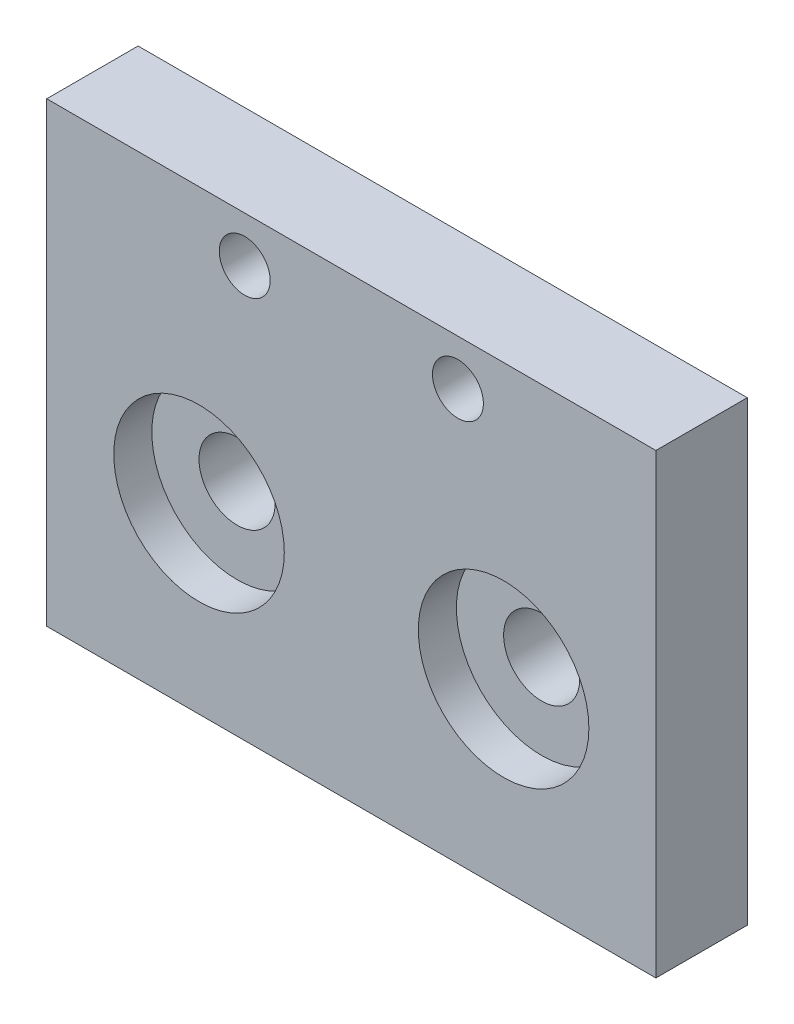
SolidWorks part; units mm, degrees
ref_plane "Front Plane" through (0, 0, 0) normal (0, 0, 1) x (1, 0, 0)
ref_plane "Top Plane" through (0, 0, 0) normal (0, 1, 0) x (1, 0, 0)
ref_plane "Right Plane" through (0, 0, 0) normal (1, 0, 0) x (0, 0, -1)
sketch "Sketch1" plane through (0, 0, 0) normal (0, 0, 1) x (1, 0, 0)
  line L0 (31.75, -9.525) -> (-31.75, -9.525) construction
  line L1 (-31.75, 0) -> (31.75, 0)
  line L2 (-31.75, 0) -> (-31.75, -47.625)
  line L3 (-31.75, -47.625) -> (31.75, -47.625)
  line L4 (31.75, 0) -> (31.75, -47.625)
  line L5 (31.75, -9.525) -> (31.75, 0) construction
  line L6 (0, -9.525) -> (0, -47.625) construction
  circle A0 centre (11.1125, -4.7625) radius 2.1 construction
  circle A1 centre (-11.1125, -4.7625) radius 2.1 construction
  circle A2 centre (11.1125, -4.7625) radius 2.1 construction
  circle A3 centre (-11.1125, -4.7625) radius 2.1 construction
  circle A4 centre (-11.1125, -4.7625) radius 2.6543
  circle A5 centre (11.1125, -4.7625) radius 2.6543
  circle A8 centre (-15.875, -28.575) radius 3.9687
  circle A9 centre (-15.875, -28.575) radius 8.89
  circle A10 centre (-171.4502, -17.4815) radius 3.9687 construction
  circle A11 centre (-171.4502, -17.4815) radius 8.89 construction
  circle A12 centre (15.875, -28.575) radius 3.9687
  circle A13 centre (15.875, -28.575) radius 8.89
  point P23 (0, -28.575)
  dimension "D2" = 5.3086
  dimension "D3" = 38.1
  dimension "D1" = 47.625
  dimension "D4" = 31.75
extrude "Boss-Extrude1" add sketch "Sketch1" along normal blind 9.525 contours L4 L1 L2 L3 A9 A5 A4 A13 | A9 A8 | A13 A12 region at (0, -23.1998, 0) region at (-24.5136, -28.575, 0) region at (7.2364, -28.575, 0)
extrude "Cut-Extrude2" cut sketch "Sketch1<3>" against normal offset from surface 5.5575 and the other way through all from surface contours A9 A8 | A13 A12 region at (-24.5136, -28.575, 0) region at (7.2364, -28.575, 0) up to face at (13.7668, -4.7625, 0) starting at face at (13.7668, -4.7625, 9.525)
sketch "Sketch1<3>" plane through (0, 0, 0) normal (0, 0, 1) x (1, 0, 0) same geometry as "Sketch1"
